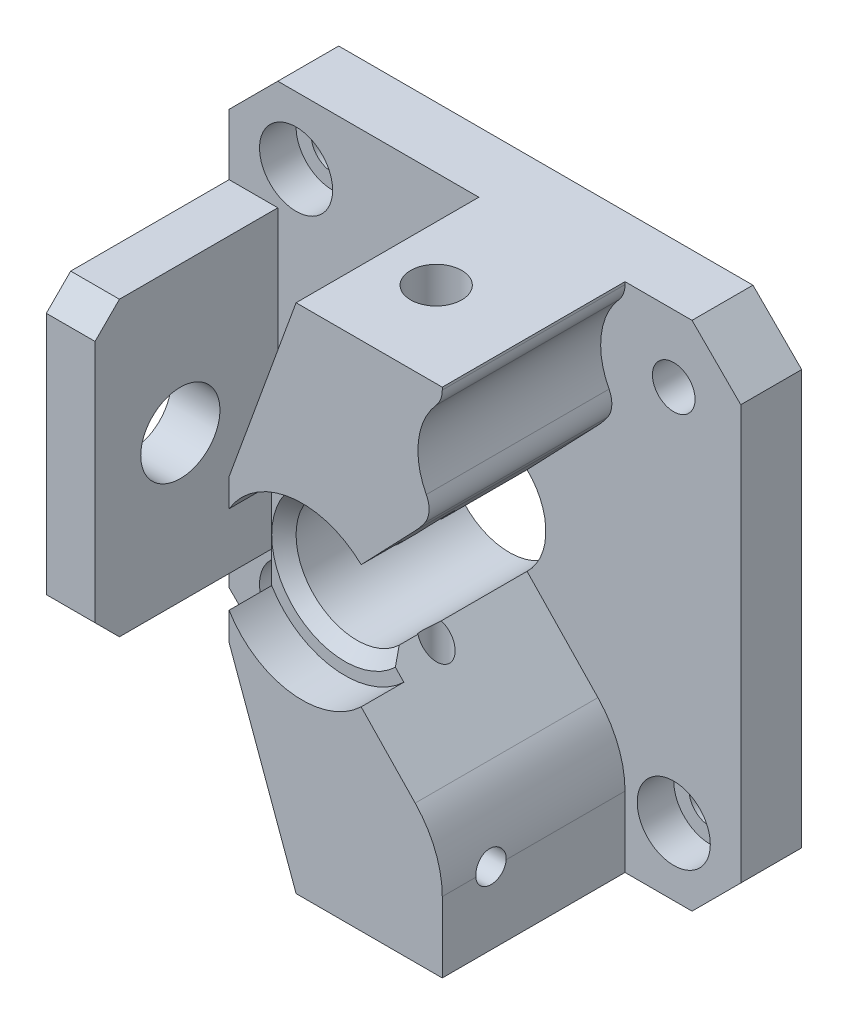
SolidWorks part; units mm, degrees
material "6063-T1"
ref_plane "Piano frontale" through (0, 0, 0) normal (0, 0, 1) x (1, 0, 0)
ref_plane "Piano superiore" through (0, 0, 0) normal (0, 1, 0) x (1, 0, 0)
ref_plane "Piano destro" through (0, 0, 0) normal (1, 0, 0) x (0, 0, -1)
ref_plane "Motor plane" through (0, 0, -20) normal (0, 0, 1) x (1, 0, 0)
sketch "Schizzo1" plane through (0, 0, -20) normal (0, 0, 1) x (1, 0, 0)
  line L1 (15.5, -15.5) -> (-15.5, -15.5) construction
  line L2 (15.5, -15.5) -> (15.5, 15.5) construction
  line L3 (15.5, 15.5) -> (-15.5, 15.5) construction
  line L4 (-15.5, -15.5) -> (-15.5, 15.5) construction
  line L5 (15.5, -15.5) -> (-15.5, 15.5) construction
  line L6 (15.5, 15.5) -> (-15.5, -15.5) construction
  line L7 (21, -21) -> (-21, -21)
  line L8 (21, -21) -> (21, 21)
  line L9 (21, 21) -> (-21, 21)
  line L10 (-21, -21) -> (-21, 21)
  line L11 (21, -21) -> (-21, 21) construction
  line L12 (21, 21) -> (-21, -21) construction
  circle A0 centre (-15.5, 15.5) radius 1.75
  circle A1 centre (15.5, 15.5) radius 1.75
  circle A2 centre (-15.5, -15.5) radius 1.75
  circle A3 centre (15.5, -15.5) radius 1.75
  dimension "D3" = 3.5
  dimension "D1" = 31
  dimension "D2" = 31
  dimension "D5" = 42
  dimension "D6" = 42
extrude "Estrusione-Estrusione1" add sketch "Schizzo1" along normal blind 5
sketch "Schizzo3" plane through (0, 0, -15) normal (0, 0, 1) x (1, 0, 0)
  line L0 (-21, -21) -> (21, -21) construction
  line L1 (11.5, -21) -> (-6, -21)
  line L2 (11.5, -21) -> (11.5, 21)
  line L3 (11.5, 21) -> (-6, 21)
  line L4 (-6, -21) -> (-6, 21)
  line L5 (21, 21) -> (-21, 21) construction
  line L6 (-21, 21) -> (-21, -21) construction
  line L7 (21, -21) -> (21, 21) construction
  dimension "D1" = 15
  dimension "D2" = 9.5
extrude "Estrusione-Estrusione4" add sketch "Schizzo3" along normal blind 15
sketch "Schizzo4" plane through (0, 0, 0) normal (0, 0, 1) x (1, 0, 0)
  circle A0 centre (0, 0) radius 5
  dimension "D1" = 10
extrude "Taglio-Estrusione1" cut sketch "Schizzo4" against normal through all
ref_plane "Piano3" through (4, 0, 0) normal (1, 0, 0) x (0, 0, -1)
sketch "Schizzo6" plane through (0, -21, 0) normal (0, -1, 0) x (1, 0, 0)
  line L0 (11.5, -7) -> (-6, -7) construction
  line L2 (-6, 0) -> (-6, -15) construction
  line L3 (4, -11) -> (4, 11) construction
  line L4 (4, -2.5823) -> (4, -27.3722) construction
  line L9 (23.1, -20) -> (-23.1, -20) construction
  circle A0 centre (4, -7) radius 1.1
  point P10 (4, -7)
  dimension "D1" = 2.2
  dimension "D2" = 13
extrude "Taglio-Estrusione3" cut sketch "Schizzo6" against normal through all
sketch "Schizzo7" plane through (0, 0, 0) normal (0, 0, 1) x (1, 0, 0)
  line L0 (11.5, 0) -> (-6, 0) construction
  line L1 (11.5, -21) -> (11.5, 21) construction
  line L2 (-6, 21) -> (-6, -21) construction
  line L3 (11.5, 12) -> (0, 0)
  line L4 (11.5, 12) -> (11.5, -12)
  line L5 (11.5, -12) -> (0, 0)
  dimension "D1" = 12
extrude "Taglio-Estrusione4" cut sketch "Schizzo7" against normal blind 15
fillet "Raccordo2" radius 8 1 edges at (11.5, 12, -7.5)
fillet "Raccordo3" radius 8 1 edges at (11.5, -12, -7.5)
chamfer "Smusso1" distance 4 angle 45 4 edges at (21, -21, -17.5) (-21, -21, -17.5) (-21, 21, -17.5) (21, 21, -17.5)
sketch "Schizzo22" plane through (11.5, 0, 0) normal (1, 0, 0) x (0, 0, -1)
  line L0 (15, -17) -> (15, 17) construction
  point P0 (4, -15.1119)
  dimension "D1" = 11
hole_wizard "Foro filettato M3-2" positions "Schizzo24" profile "Schizzo23" tap size "M3" standard "ISO"
sketch "Schizzo24" plane through (11.5, 0, 0) normal (1, 0, 0) x (0, 0, -1)
  point P0 (4, -15.1119)
sketch "Schizzo23" plane through (11.5, -15.1119, -4) normal (0, 1, 0) x (0, 0, -1)
  line L0 (0, 0) -> (0, 12.7511)
  line L1 (0, 12.7511) -> (1.25, 12)
  line L2 (1.25, 12) -> (1.25, 0)
  line L5 (1.25, 0) -> (0, 0)
  line L10 (0, 12.7511) -> (-1.25, 12) construction
  line L11 (0, -6.35) -> (0, 107.95) construction
  dimension "Tap Drill Dia." = 2.5
  dimension "Tap Drill Depth" = 12
  dimension "Drill Angle" = 118
cosmetic thread "Filettatura del foro2" parameters "D1"=6, "D2"=3
sketch "Schizzo28" plane through (0, 0, -15) normal (0, 0, 1) x (1, 0, 0)
  line L1 (-21, 0) -> (21, 0) construction
  line L2 (-21, 17) -> (-21, -17) construction
  line L3 (21, -17) -> (21, 17) construction
  line L4 (-21, -12) -> (-21, 12)
  line L6 (-21, 12) -> (-17, 12)
  line L7 (-17, 12) -> (-17, -12)
  line L8 (-21, -12) -> (-17, -12)
  point P13 (-17, 0)
  dimension "D1" = 4
  dimension "D2" = 12
extrude "Estrusione-Estrusione5" add sketch "Schizzo28" along normal blind 15
sketch "Schizzo29" plane through (0, 0, -15) normal (0, 0, 1) x (1, 0, 0)
  circle A0 centre (-15.5, 15.5) radius 3
  circle A1 centre (-15.5, -15.5) radius 3
  circle A2 centre (15.5, -15.5) radius 3
  dimension "D1" = 6
extrude "Taglio-Estrusione6" cut sketch "Schizzo29" against normal blind 3
chamfer "Smusso3" distance 5.5 angle 70 2 edges first distance on face at (5.1, -21, -7) first distance on face at (5.1, 21, -7)
sketch "Schizzo30" plane through (-21, 0, 0) normal (-1, 0, 0) x (0, 0, 1)
  line L0 (0, 0) -> (-20, 0) construction
  line L1 (0, 12) -> (0, -12) construction
  line L2 (-20, -23.1) -> (-20, 23.1) construction
  circle A0 centre (-7, 0) radius 3.25
  dimension "D1" = 6.5
  dimension "D2" = 7
extrude "Taglio-Estrusione7" cut sketch "Schizzo30" against normal blind 4
chamfer "Smusso4" distance 2 angle 45 2 edges at (-19, -12, 0) (-19, 12, 0)
hole_wizard "Foro filettato M5-1" positions "Schizzo3D1" profile "Schizzo31" tap size "M5" standard "ISO"
sketch3d "Schizzo3D1"
  line L0 (4, 21, -7) -> (4, 3.6099, -7) construction
  point P0 (4, 21, -7)
sketch "Schizzo31" plane through (4, 21, -7) normal (1, 0, 0) x (0, 0, 1)
  line L0 (0, 0) -> (0, 6.2618)
  line L1 (0, 6.2618) -> (2.1, 5)
  line L2 (2.1, 5) -> (2.1, 0)
  line L5 (2.1, 0) -> (0, 0)
  line L10 (0, 6.2618) -> (-2.1, 5) construction
  line L11 (0, -6.35) -> (0, 107.95) construction
  dimension "Tap Drill Dia." = 4.2
  dimension "Tap Drill Depth" = 5
  dimension "Drill Angle" = 118
cosmetic thread "Filettatura del foro3" parameters "D1"=5, "D2"=5
sketch "Schizzo32" plane through (0, 0, 0) normal (0, 0, 1) x (1, 0, 0)
  circle A0 centre (0, 0) radius 7
  dimension "D1" = 14
extrude "Taglio-Estrusione8" cut sketch "Schizzo32" against normal blind 3.5
sketch "Schizzo33" plane through (0, 0, -20) normal (0, 0, -1) x (-1, 0, 0)
  circle A0 centre (0, 0) radius 12
  dimension "D1" = 24
extrude "Taglio-Estrusione9" cut sketch "Schizzo33" against normal blind 3
sketch "Schizzo34" plane through (0, 0, 0) normal (0, 0, 1) x (1, 0, 0)
  circle A0 centre (15.5, 15.5) radius 6
  dimension "D1" = 12
extrude "Taglio-Estrusione10" cut sketch "Schizzo34" along direction (0, 0, 1) on the side against the normal blind 15
fillet "Raccordo4" radius 2 1 edges at (11.5, 19.9721, -7.5)
fillet "Raccordo5" radius 2 1 edges at (10.7505, 11.8336, -7.5)
chamfer "Smusso5" distance 1 angle 45 1 edges at (-5, 0, -3.5)
